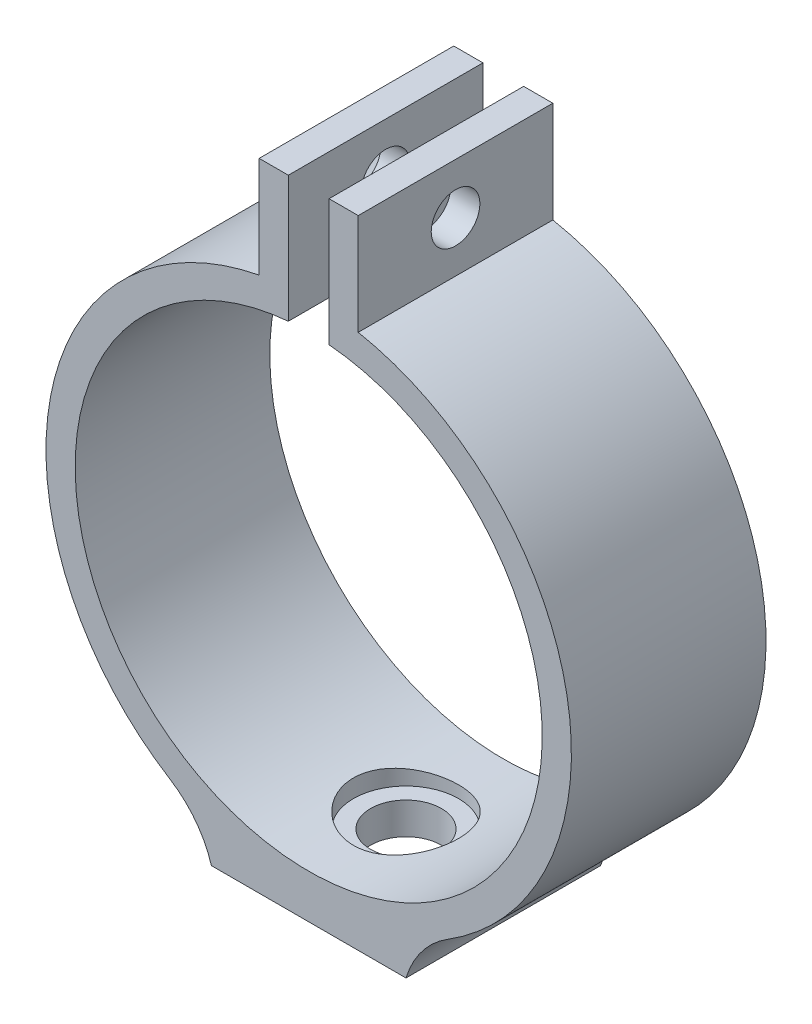
SolidWorks part; units mm, degrees
ref_plane "Front Plane" through (0, 0, 0) normal (0, 0, 1) x (1, 0, 0)
ref_plane "Top Plane" through (0, 0, 0) normal (0, 1, 0) x (1, 0, 0)
ref_plane "Right Plane" through (0, 0, 0) normal (1, 0, 0) x (0, 0, -1)
sketch "Sketch2" plane through (0, 0, 0) normal (0, 0, 1) x (1, 0, 0)
  line L0 (-2.0917, 23.9087) -> (-2.3532, 26.8973) construction
  line L1 (2.0917, 23.9087) -> (2.3532, 26.8973) construction
  line L2 (0, 0) -> (0, -24) construction
  line L3 (0, -24) -> (0, -28.5) construction
  line L5 (-10, -25.0799) -> (-10, -28.5)
  line L6 (-10, -28.5) -> (10, -28.5)
  line L7 (10, -25.0799) -> (10, -28.5)
  line L8 (-13.9653, -23.1078) -> (10, -28.5) construction
  line L9 (-10, -28.5) -> (10.3248, -23.9269) construction
  line L10 (2.0917, 23.9087) -> (2.0917, 36.9087)
  line L11 (2.0917, 36.9087) -> (5.0917, 36.9087)
  line L12 (5.0917, 36.9087) -> (5.0917, 26.5155)
  line L13 (-2.0917, 23.9087) -> (-2.0917, 36.9087)
  line L14 (-2.0917, 36.9087) -> (-5.0917, 36.9087)
  line L15 (-5.0917, 36.9087) -> (-5.0917, 26.5155)
  arc A0 (-2.0917, 23.9087) -> (2.0917, 23.9087) centre (0, 0) ccw
  arc A1 (-5.0917, 26.5155) -> (-10, -25.0799) centre (0, 0) ccw
  arc A2 (10, -25.0799) -> (5.0917, 26.5155) centre (0, 0) ccw
  point P11 (0, -26.25)
  dimension "D1" = 48
  dimension "D2" = 3
  dimension "D3" = 175
  dimension "D4" = 175
  dimension "D5" = 20
  dimension "D6" = 4.5
  dimension "D7" = 3
  dimension "D8" = 13
  dimension "D9" = 3
  dimension "D10" = 13
extrude "Boss-Extrude1" add sketch "Sketch2" along normal blind 20
fillet "Fillet1" radius 10 2 edges at (10, -25.0799, 10) (-10, -25.0799, 10)
ref_plane "Plane1" through (0, -24, 0) normal (0, 1, 0) x (1, 0, 0)
sketch "Sketch3" plane through (0, -24, 0) normal (0, 1, 0) x (1, 0, 0)
  line L0 (0, 0) -> (0, -20) construction
  line L1 (-24, -20) -> (24, -20) construction
  circle A1 centre (0, -10) radius 5.4
  point P7 (-11.9783, -10)
  point P8 (0, -10)
  dimension "D1" = 10.8
extrude "Cut-Extrude3" cut sketch "Sketch3" against normal offset from surface 3.27 and the other way blind 20 up to face at (0, -28.5, 10)
sketch "Sketch4" plane through (0, -25.23, 0) normal (0, 1, 0) x (1, 0, 0)
  circle A0 centre (0, -10) radius 3.64
  dimension "D1" = 7.28
extrude "Cut-Extrude4" cut sketch "Sketch4" against normal through all
sketch "Sketch5" plane through (-5.0917, 0, 0) normal (-1, 0, 0) x (0, 0, 1)
  line L0 (0, 36.9087) -> (20, 26.5155) construction
  line L1 (0, 26.5155) -> (20, 36.9087) construction
  circle A0 centre (10, 31.7121) radius 2.5
  dimension "D1" = 5
extrude "Cut-Extrude5" cut sketch "Sketch5" against normal through all
